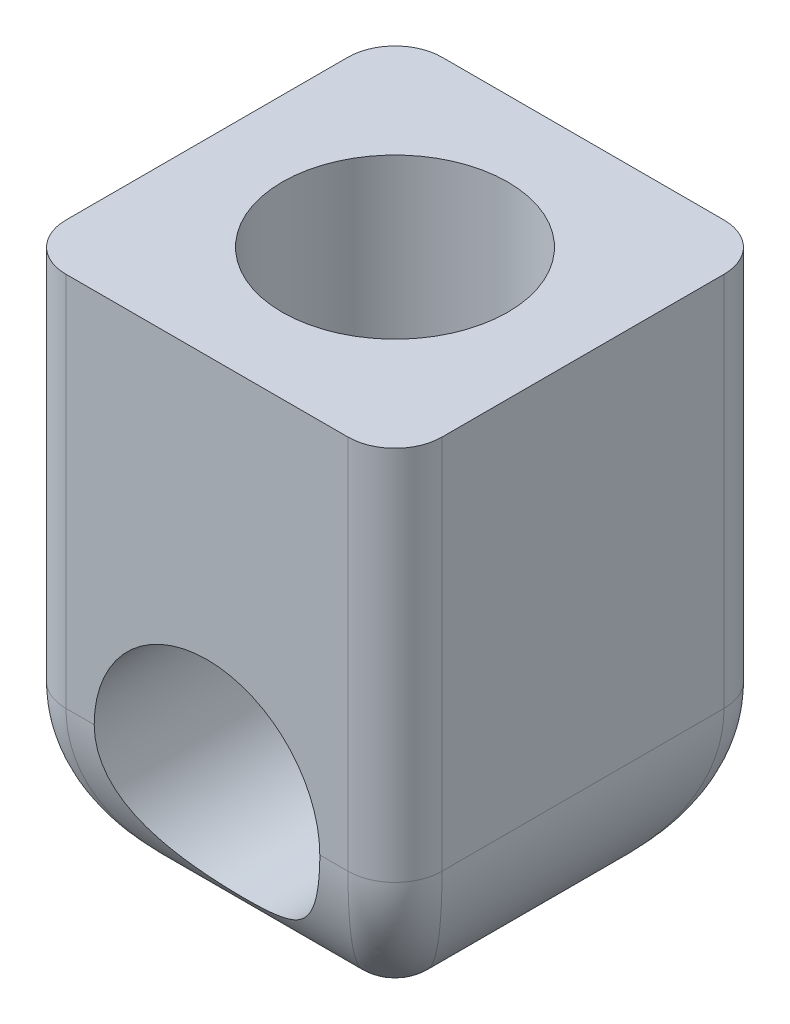
SolidWorks part; units mm, degrees
ref_plane "Front Plane" through (0, 0, 0) normal (0, 0, 1) x (1, 0, 0)
ref_plane "Top Plane" through (0, 0, 0) normal (0, 1, 0) x (1, 0, 0)
ref_plane "Right Plane" through (0, 0, 0) normal (1, 0, 0) x (0, 0, -1)
sketch "Sketch1" plane through (0, 0, 0) normal (0, 1, 0) x (1, 0, 0)
  line L1 (20, -20) -> (-20, -20)
  line L2 (20, -20) -> (20, 20)
  line L3 (20, 20) -> (-20, 20)
  line L4 (-20, -20) -> (-20, 20)
  line L5 (20, -20) -> (-20, 20) construction
  line L6 (20, 20) -> (-20, -20) construction
  point P0 (0, 0)
  dimension "D1" = 40
  dimension "D2" = 40
extrude "Boss-Extrude1" add sketch "Sketch1" along normal blind 60
sketch "Sketch2" plane through (0, 0, 20) normal (0, 0, 1) x (1, 0, 0)
  line L0 (-20, 0) -> (20, 0) construction
  line L2 (-20, 60) -> (-20, 0) construction
  circle A0 centre (0, 20) radius 12
  dimension "D1" = 24
  dimension "D2" = 20
  dimension "D3" = 20
extrude "Cut-Extrude1" cut sketch "Sketch2" against normal blind 100
sketch "Sketch3" plane through (0, 60, 0) normal (0, 1, 0) x (1, 0, 0)
  circle A0 centre (0, 0) radius 12
  dimension "D1" = 24
extrude "Cut-Extrude2" cut sketch "Sketch3" against normal blind 20
fillet "Fillet1" radius 5 4 edges at (20, 30, -20) (20, 30, 20) (-20, 30, -20) (-20, 30, 20)
fillet "Fillet2" radius 20 8 edges at (18.5355, 0, 18.5355) (0, 0, 20) (-18.5355, 0, 18.5355) (-18.5355, 0, -18.5355) (0, 0, -20) (18.5355, 0, -18.5355) (-20, 0, 0) (20, 0, 0)
